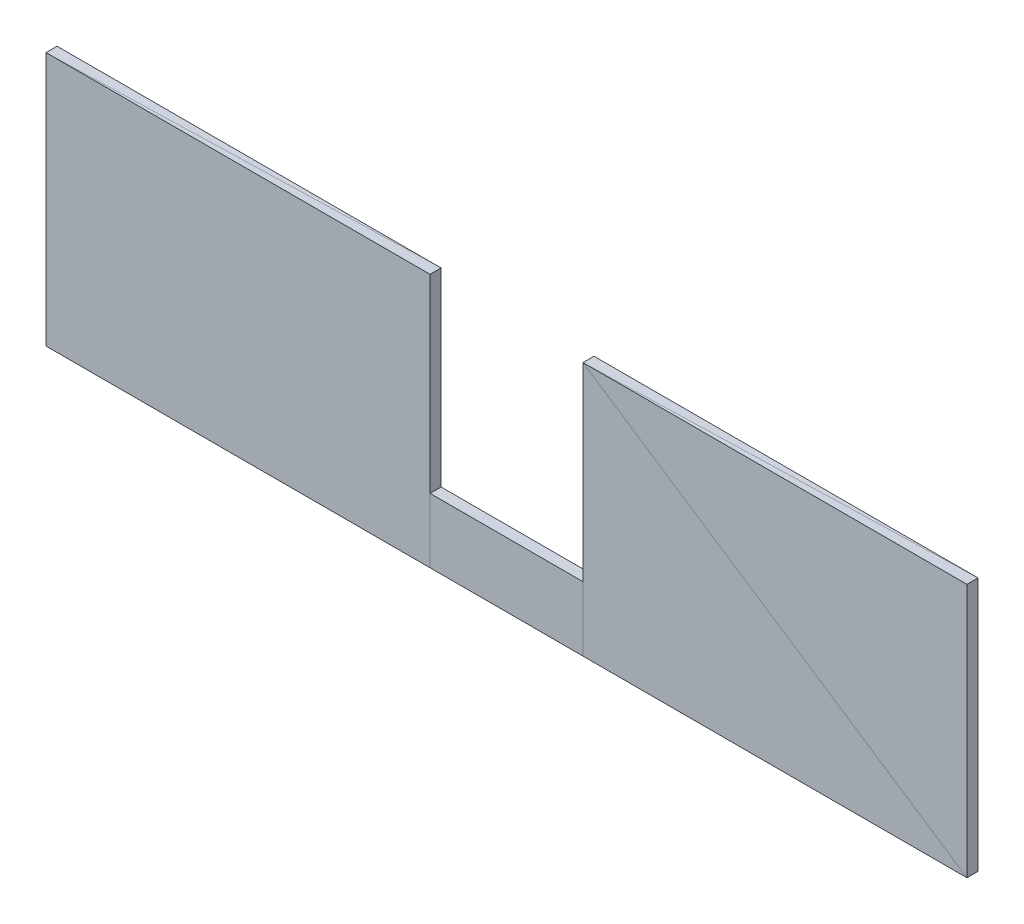
SolidWorks part; units mm, degrees
material "Pine"
ref_plane "Front Plane" through (0, 0, 0) normal (0, 0, 1) x (1, 0, 0)
ref_plane "Top Plane" through (0, 0, 0) normal (0, 1, 0) x (1, 0, 0)
ref_plane "Right Plane" through (0, 0, 0) normal (1, 0, 0) x (0, 0, -1)
sketch "Sketch1" plane through (0, 0, 0) normal (0, 0, 1) x (1, 0, 0)
  line L6 (0, 0) -> (1000, 0)
  line L10 (0, 0) -> (0, 276)
  line L11 (0, 276) -> (1000, 276)
  line L12 (1000, 0) -> (1000, 276)
  dimension "D3" = 276
  dimension "D1" = 1000
extrude "Boss-Extrude1" add sketch "Sketch1" along normal blind 12 contours L10 L11 L12 L6
sketch "Sketch2" plane through (0, 0, 12) normal (0, 0, 1) x (1, 0, 0)
  line L0 (500, 276) -> (500, 0) construction
  line L1 (0, 276) -> (1000, 276) construction
  line L2 (0, 0) -> (1000, 0) construction
  line L4 (417, 276) -> (583, 276)
  line L5 (417, 276) -> (417, 0)
  line L6 (417, 0) -> (583, 0)
  line L7 (583, 276) -> (583, 0)
  line L8 (417, 276) -> (583, 0) construction
  line L9 (417, 0) -> (583, 276) construction
  point P6 (500, 138)
  dimension "D1" = 166
extrude "Cut-Extrude1" cut sketch "Sketch2" against normal up to surface (12 mm away)
sketch "Sketch3" plane through (0, 0, 0) normal (0, 0, 1) x (1, 0, 0)
  line L0 (500, 173) -> (500, -103) construction
  line L4 (417, 70) -> (583, 70)
  line L5 (417, 70) -> (417, 0)
  line L6 (417, 0) -> (583, 0)
  line L7 (583, 70) -> (583, 0)
  line L8 (417, 70) -> (583, 0) construction
  line L9 (417, 0) -> (583, 70) construction
  point P6 (500, 35)
  dimension "D1" = 166
  dimension "D2" = 70
extrude "Boss-Extrude2" add sketch "Sketch3" along normal blind 12 separate body
sketch "Sketch5" plane through (0, 0, 0) normal (0, 0, 1) x (1, 0, 0)
  line L0 (0, 276) -> (417, 276) construction
  line L1 (0, 0) -> (417, 0)
  line L2 (0, 0) -> (0, 276)
  line L3 (0, 276) -> (417, 276)
  line L4 (417, 0) -> (417, 276)
  dimension "D1" = 417
extrude "Boss-Extrude3" add sketch "Sketch5" along normal blind 12 separate body
sketch "Sketch6" plane through (0, 0, 0) normal (0, 0, 1) x (1, 0, 0)
  line L0 (417, 276) -> (0, 276) construction
  line L1 (583, 0) -> (1000, 0)
  line L2 (583, 0) -> (583, 276)
  line L3 (583, 276) -> (1000, 276)
  line L4 (1000, 0) -> (1000, 276)
  line L5 (417, 0) -> (583, 0) construction
  point P6 (583, 0)
  dimension "D1" = 417
extrude "Boss-Extrude4" add sketch "Sketch6" along normal blind 12 separate body
equation "\"LENGTH\" = 1000mm"
equation "\"D1@Sketch1\"=\"LENGTH\""
equation "\"PLY\"= 12mm"
equation "\"D1@Boss-Extrude1\"=\"PLY\""
equation "\"CENTER_BRACE_LENGTH\" = 393mm"
equation "\"D1@Sketch2\"=\"LENGTH\" - \"CENTER_BRACE_LENGTH\" * 2 - \"PLY\" * 4"
equation "\"PANEL_WIDTH\"= \"LENGTH\" - \"CENTER_BRACE_LENGTH\" * 2 - \"PLY\" * 4"
equation "\"D1@Boss-Extrude2\"=\"PLY\""
equation "\"D1@Sketch5\"=\"LENGTH\"/2 - \"PANEL_WIDTH\"/2"
equation "\"D1@Boss-Extrude3\"=\"PLY\""
equation "\"D1@Sketch6\"=\"LENGTH\"/2 - \"PANEL_WIDTH\"/2"
equation "\"D1@Boss-Extrude4\"=\"PLY\""
